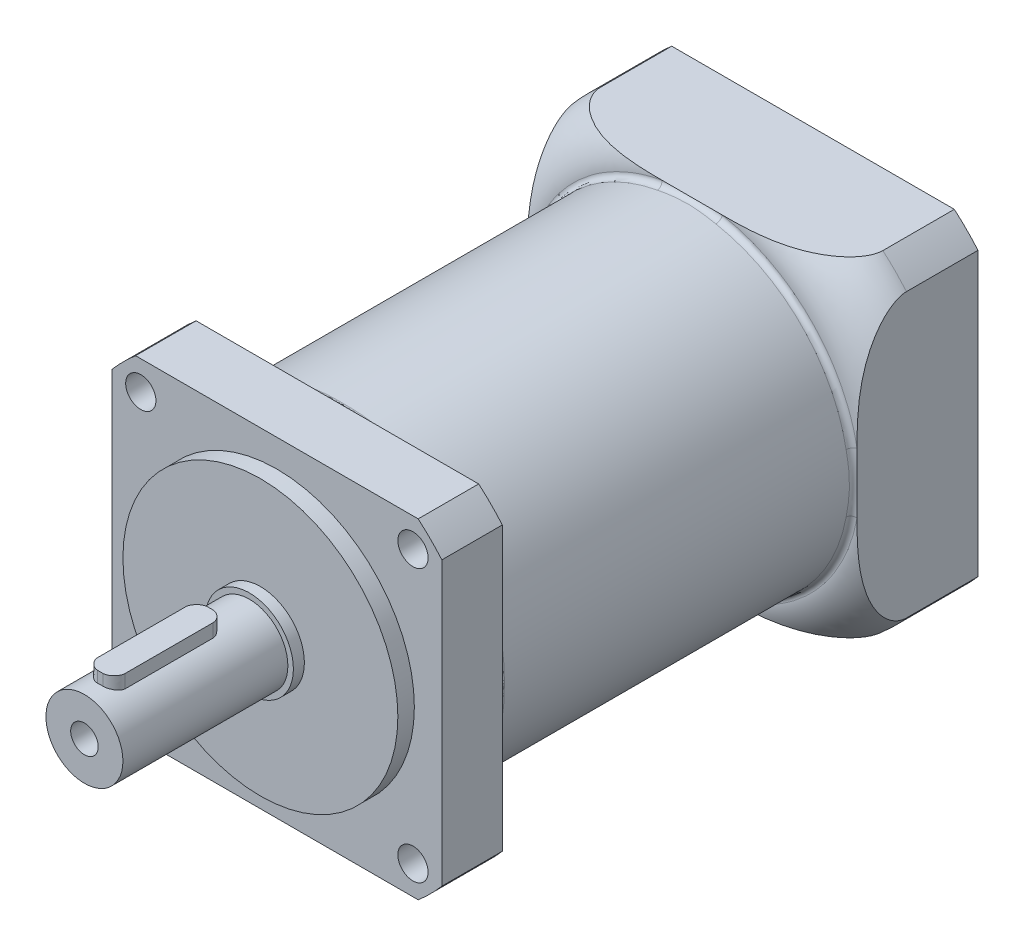
SolidWorks part; units mm, degrees
material "Acier non allié"
ref_plane "Plan de face" through (0, 0, 0) normal (0, 0, 1) x (1, 0, 0)
ref_plane "Plan de dessus" through (0, 0, 0) normal (0, 1, 0) x (1, 0, 0)
ref_plane "Plan de droite" through (0, 0, 0) normal (1, 0, 0) x (0, 0, -1)
sketch "Esquisse1" plane through (0, 0, 0) normal (0, 0, 1) x (1, 0, 0)
  line L1 (30, 30) -> (-30, 30)
  line L2 (30, 30) -> (30, -30)
  line L3 (30, -30) -> (-30, -30)
  line L4 (-30, 30) -> (-30, -30)
  line L5 (30, 30) -> (-30, -30) construction
  line L6 (30, -30) -> (-30, 30) construction
  point P0 (0, 0)
  dimension "D1" = 60
extrude "Boss.-Extru.1" add sketch "Esquisse1" along normal blind 22
sketch "Esquisse3" plane through (0, 0, 22) normal (0, 0, 1) x (1, 0, 0)
  circle A0 centre (0, 0) radius 29.5
  dimension "D1" = 59
extrude "Boss.-Extru.2" add sketch "Esquisse3" along normal blind 64.5
sketch "Esquisse4" plane through (0, 0, 86.5) normal (0, 0, 1) x (1, 0, 0)
  line L4 (-30, 30) -> (-30, -30)
  line L5 (30, 30) -> (-30, 30)
  line L6 (30, -30) -> (30, 30)
  line L7 (-30, -30) -> (30, -30)
  line L8 (-30, 30) -> (-30, -30)
  line L9 (30, 30) -> (-30, 30)
  line L10 (30, -30) -> (30, 30)
  line L11 (-30, -30) -> (30, -30)
  dimension "D1" = 0
extrude "Boss.-Extru.3" add sketch "Esquisse4" along normal blind 11
sketch "Esquisse5" plane through (0, 0, 97.5) normal (0, 0, 1) x (1, 0, 0)
  circle A0 centre (0, 0) radius 25
  dimension "D1" = 50
extrude "Boss.-Extru.4" add sketch "Esquisse5" along normal blind 3
sketch "Esquisse6" plane through (0, 0, 97.5) normal (0, 0, 1) x (1, 0, 0)
  circle A0 centre (0, 0) radius 39.5
  dimension "D1" = 79
extrude "Enlèv. mat.-Extru.1" cut sketch "Esquisse6" against normal through all flip side to cut
sketch "Esquisse7" plane through (0, 0, 97.5) normal (0, 0, 1) x (1, 0, 0)
  line L0 (27.9307, 27.9307) -> (0, 0) construction
  circle A0 centre (0, 0) radius 35 construction
  arc A1 (30, 25.6953) -> (25.6953, 30) centre (0, 0) ccw construction
  circle A2 centre (24.7487, 24.7487) radius 2.75
  circle A3 centre (24.7487, -24.7487) radius 2.75
  circle A4 centre (-24.7487, -24.7487) radius 2.75
  circle A5 centre (-24.7487, 24.7487) radius 2.75
  dimension "D1" = 70
  dimension "D2" = 5.5
  dimension "D3" = 4
extrude "Enlèv. mat.-Extru.2" cut sketch "Esquisse7" against normal up to surface (11 mm away) up to face at (29.5, 0, 86.5)
fillet "Congé1" radius 1 1 edges at (29.5, 0, 86.5)
sketch "Esquisse8" plane through (0, 0, 0) normal (0, 0, -1) x (-1, 0, 0)
  line L0 (0, 0) -> (27.9307, 27.9307) construction
  circle A0 centre (0, 0) radius 33.35 construction
  arc A1 (30, 25.6953) -> (25.6953, 30) centre (0, 0) ccw construction
  circle A2 centre (23.582, 23.582) radius 2
  circle A3 centre (23.582, -23.582) radius 2
  circle A4 centre (-23.582, -23.582) radius 2
  circle A5 centre (-23.582, 23.582) radius 2
  dimension "D1" = 66.7
  dimension "D2" = 4
  dimension "D3" = 4
extrude "Enlèv. mat.-Extru.3" cut sketch "Esquisse8" against normal blind 8
fillet "Congé2" radius 9 4 edges at (27.9307, -27.9307, 22) (27.9307, 27.9307, 22) (-27.9307, -27.9307, 22) (-27.9307, 27.9307, 22) conic rho 0.35
fillet "Congé3" radius 1 1 edges at (29.5, 0, 22)
sketch "Esquisse9" plane through (0, 0, 100.5) normal (0, 0, 1) x (1, 0, 0)
  circle A0 centre (0, 0) radius 7
  dimension "D1" = 14
extrude "Boss.-Extru.5" add sketch "Esquisse9" along normal blind 32
sketch "Esquisse10" plane through (0, 0, 100.5) normal (0, 0, 1) x (1, 0, 0)
  circle A0 centre (0, 0) radius 8
  dimension "D1" = 16
extrude "Boss.-Extru.6" add sketch "Esquisse10" along normal blind 2
sketch "Esquisse11" plane through (0, 0, 0) normal (0, 0, -1) x (-1, 0, 0)
  circle A0 centre (0, 0) radius 19.05
  dimension "D1" = 38.1
extrude "Enlèv. mat.-Extru.4" cut sketch "Esquisse11" against normal blind 4
sketch "Esquisse12" plane through (0, 0, 4) normal (0, 0, -1) x (-1, 0, 0)
  circle A0 centre (0, 0) radius 4
  dimension "D1" = 8
extrude "Enlèv. mat.-Extru.5" cut sketch "Esquisse12" against normal blind 27
ref_plane "Plan1" through (0, 0, 129.5) normal (0, 0, 1) x (1, 0, 0)
sketch "Esquisse13" plane through (0, 0, 129.5) normal (0, 0, 1) x (1, 0, 0)
  line L1 (-2.6034, 9) -> (2.3966, 9)
  line L2 (-2.6034, 9) -> (-2.6034, 1.9077)
  line L3 (-2.6034, 1.9077) -> (2.3966, 1.9077)
  line L4 (2.3966, 9) -> (2.3966, 1.9077)
  dimension "D1" = 5
  dimension "D2" = 9
extrude "Boss.-Extru.7" add sketch "Esquisse13" against normal blind 20 separate body
fillet "Congé4" radius 2 4 edges at (-2.6034, 5.4539, 109.5) (2.3966, 5.4539, 129.5) (2.3966, 5.4539, 109.5) (-2.6034, 5.4539, 129.5) conic rho 0.35
sketch "Esquisse14" plane through (0, 0, 132.5) normal (0, 0, 1) x (1, 0, 0)
  circle A0 centre (0, 0) radius 2.5
  dimension "D1" = 5
extrude "Enlèv. mat.-Extru.6" cut sketch "Esquisse14" against normal blind 18
sketch "Esquisse15" plane through (0, 0, 4) normal (0, 0, -1) x (-1, 0, 0)
  circle A0 centre (0, 0) radius 15
  circle A1 centre (0, 0) radius 13
  dimension "D1" = 30
  dimension "D2" = 26
extrude "Enlèv. mat.-Extru.7" cut sketch "Esquisse15" against normal blind 2
